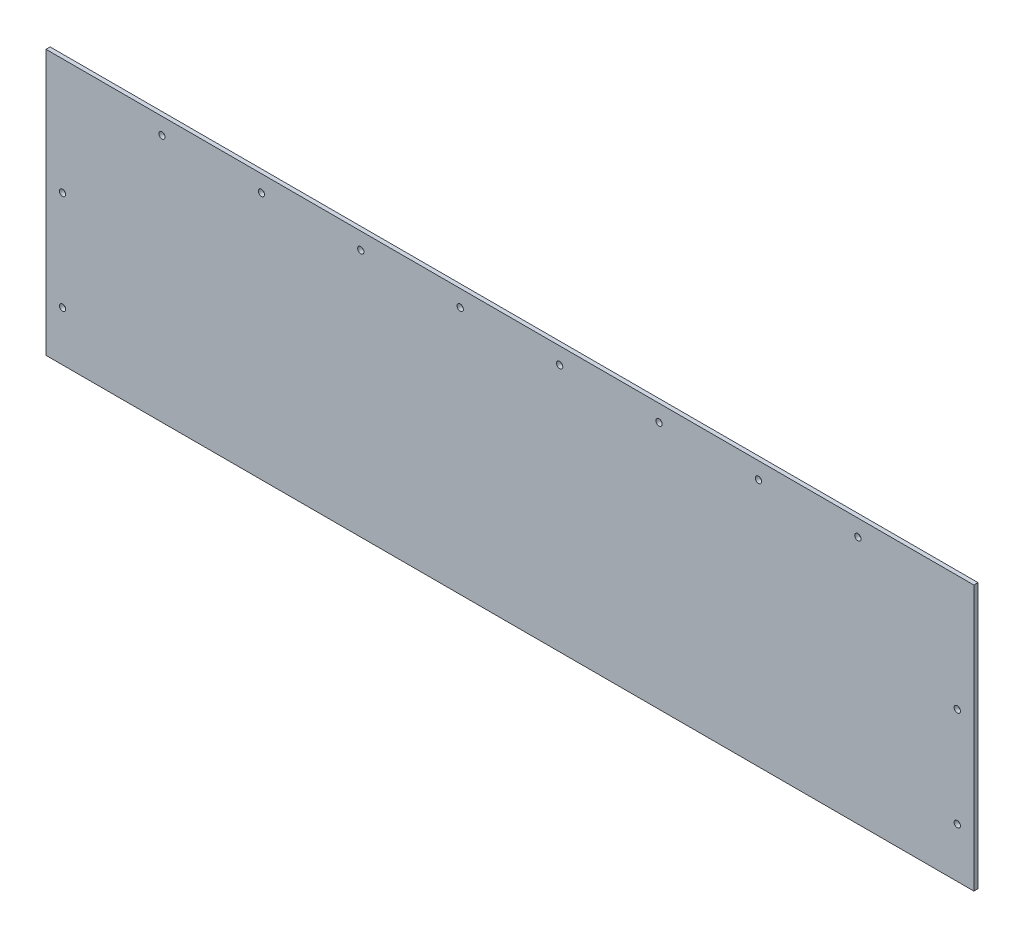
SolidWorks part; units mm, degrees
ref_plane "Front Plane" through (0, 0, 0) normal (0, 0, 1) x (1, 0, 0)
ref_plane "Top Plane" through (0, 0, 0) normal (0, 1, 0) x (1, 0, 0)
ref_plane "Right Plane" through (0, 0, 0) normal (1, 0, 0) x (0, 0, -1)
sketch "Sketch1" plane through (0, 0, 0) normal (0, 0, 1) x (1, 0, 0)
  line L1 (0, 0) -> (711.2, 0)
  line L2 (0, 0) -> (0, 203.2)
  line L3 (0, 203.2) -> (711.2, 203.2)
  line L4 (711.2, 0) -> (711.2, 203.2)
  dimension "D1" = 203.2
  dimension "D2" = 711.2
extrude "Boss-Extrude1" add sketch "Sketch1" along normal blind 3.175
sketch "Sketch2" plane through (0, 0, 3.175) normal (0, 0, 1) x (1, 0, 0)
  line L0 (0, 190.5) -> (711.2, 190.5) construction
  line L1 (0, 203.2) -> (0, 0) construction
  line L2 (711.2, 0) -> (711.2, 203.2) construction
  line L4 (711.2, 203.2) -> (0, 203.2) construction
  line L5 (698.5, 203.2) -> (698.5, 0) construction
  line L7 (12.7, 203.2) -> (12.7, 0) construction
  line L8 (0, 0) -> (711.2, 0) construction
  circle A0 centre (698.5, 190.5) radius 2.413 construction
  circle A1 centre (12.7, 190.5) radius 2.413 construction
  circle A2 centre (12.7, 114.3) radius 2.413
  circle A3 centre (698.5, 114.3) radius 2.413
  circle A4 centre (12.7, 38.1) radius 2.413
  circle A5 centre (698.5, 38.1) radius 2.413
  circle A6 centre (88.9, 190.5) radius 2.413
  circle A7 centre (165.1, 190.5) radius 2.413
  circle A8 centre (241.3, 190.5) radius 2.413
  circle A9 centre (622.3, 190.5) radius 2.413
  circle A10 centre (546.1, 190.5) radius 2.413
  circle A11 centre (469.9, 190.5) radius 2.413
  circle A12 centre (393.7, 190.5) radius 2.413
  circle A13 centre (317.5, 190.5) radius 2.413
  point P14 (12.7, 190.5)
  point P15 (698.5, 190.5)
  dimension "D4" = 4.826
  dimension "D5" = 4.826
  dimension "D1" = 12.7
  dimension "D2" = 12.7
  dimension "D3" = 12.7
  dimension "D6" = 3
  dimension "D7" = 5
  dimension "D8" = 5
extrude "Cut-Extrude1" cut sketch "Sketch2" against normal up to next
